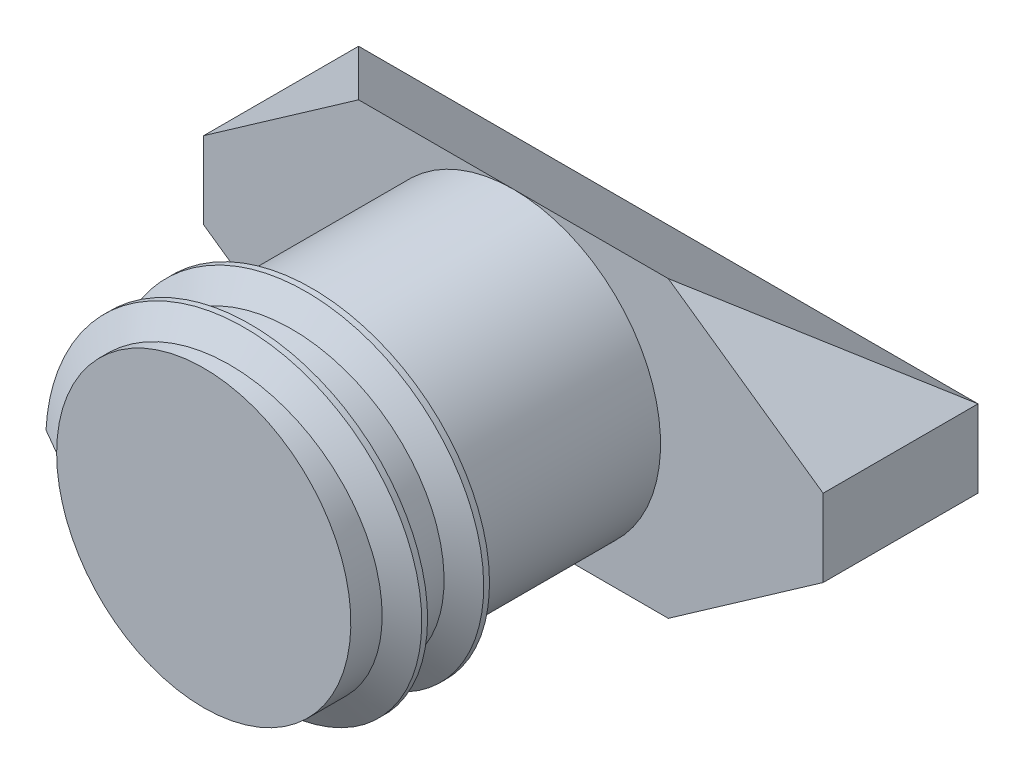
SolidWorks part; units mm, degrees
ref_plane "Front Plane" through (0, 0, 0) normal (0, 0, 1) x (1, 0, 0)
ref_plane "Top Plane" through (0, 0, 0) normal (0, 1, 0) x (1, 0, 0)
ref_plane "Right Plane" through (0, 0, 0) normal (1, 0, 0) x (0, 0, -1)
sketch "Sketch1" plane through (0, 0, 0) normal (0, 0, 1) x (1, 0, 0)
  circle A0 centre (0, 0) radius 4.75
  dimension "D1" = 9.5
extrude "Boss-Extrude1" add sketch "Sketch1" along normal blind 10
sketch "Sketch3" plane through (0, 0, 0) normal (0, 0, -1) x (-1, 0, 0)
  line L1 (-10, -4.75) -> (10, -4.75)
  line L2 (-10, -4.75) -> (-10, 4.75)
  line L3 (-10, 4.75) -> (10, 4.75)
  line L4 (10, -4.75) -> (10, 4.75)
  line L5 (-10, -4.75) -> (10, 4.75) construction
  line L6 (-10, 4.75) -> (10, -4.75) construction
  circle A0 centre (0, 0) radius 4.75 construction
  point P0 (0, 0)
  dimension "D1" = 20
extrude "Boss-Extrude3" add sketch "Sketch3" along normal blind 5
chamfer "Chamfer1" distance 5 angle 35 6 edges at (10, 4.75, -2.5) (-10, 4.75, -2.5) (0, 4.75, -5) (10, -4.75, -2.5) (-10, -4.75, -2.5) (0, -4.75, -5) first distance on face at (0, 4.75, -2) first distance on face at (0, -4.75, -2)
thread "Thread1" pitch 1.5 method extrude profile "Thread Profile1" start angle 0, offset 0, length 3.5, pitch 2, diameter 9.5
ref_plane "Plane1" through (-4.75, 0, 10) normal (0, -1, 0) x (-1, 0, 0)
sketch "Thread Profile1" plane through (-4.75, 0, 10) normal (0, -1, 0) x (-1, 0, 0)
  line L0 (0, 0) -> (0, 1.5) construction
  line L1 (0, 0) -> (0.8119, 0.4687)
  line L2 (0.8119, 0.4687) -> (0.8119, 0.6562)
  line L3 (0.8119, 0.6562) -> (0, 1.125)
  line L4 (0.8119, 0.5625) -> (0, 0.5625) construction
  line L11 (0, 0) -> (0, 1.125)
  point P2 (0, 0)
  dimension "Pitch" = 1.5
  dimension "Profile_Angle" = 60
  dimension "Profile_Land" = 0.1875
  dimension "Profile_Height" = 0.8119
